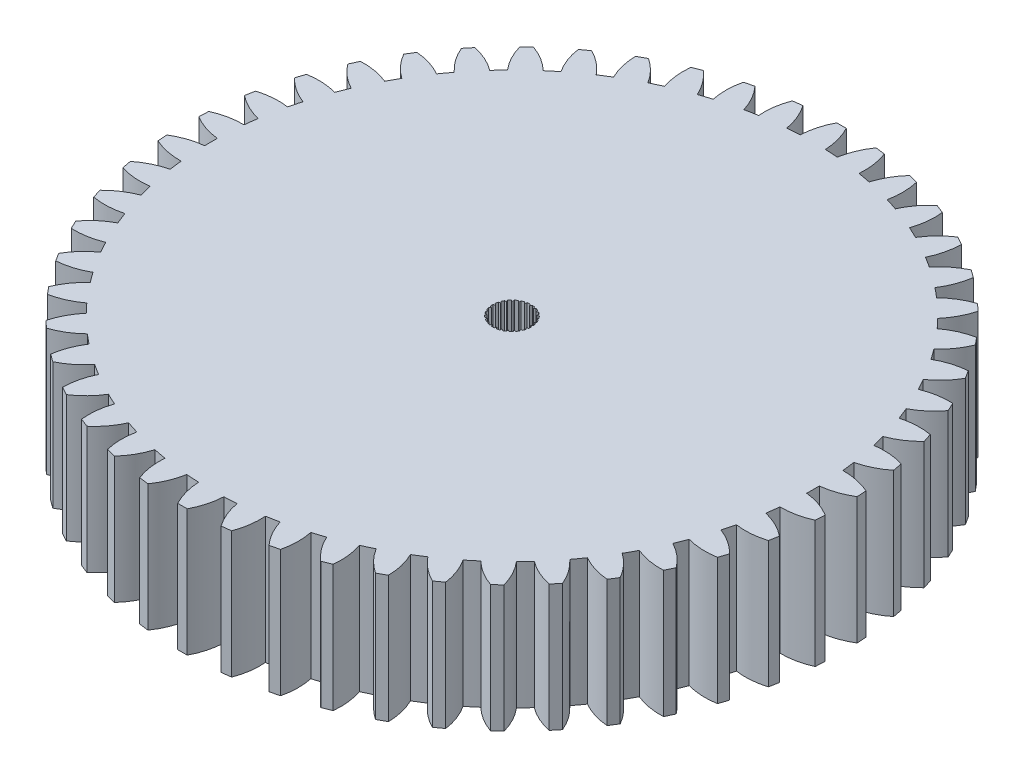
SolidWorks part; units mm, degrees
ref_plane "Front Plane" through (0, 0, 0) normal (0, 0, 1) x (1, 0, 0)
ref_plane "Top Plane" through (0, 0, 0) normal (0, 1, 0) x (1, 0, 0)
ref_plane "Right Plane" through (0, 0, 0) normal (1, 0, 0) x (0, 0, -1)
sketch "Sketch2" plane through (0, 0, 0) normal (0, 1, 0) x (1, 0, 0)
  line L0 (0, -10.2886) -> (0, 10.2886) construction
  line L1 (0, 0) -> (0.6267, 4.1579) construction
  line L2 (0, 0) -> (-0.6267, 4.1579) construction
  line L3 (0, 0) -> (0.5497, 17.4914) construction
  line L4 (0, 0) -> (-0.5497, 17.4914) construction
  line L5 (-0.1565, 3.046) -> (0, 2.775)
  line L6 (0, 2.775) -> (0.1565, 3.046)
  line L7 (-0.75, 51.9946) -> (0.75, 51.9946)
  line L8 (0.6901, 2.6878) -> (0.909, 2.9114)
  line L9 (7.8676, 46.3212) -> (7.9539, 46.8293)
  line L10 (3.8992, 46.8226) -> (3.9419, 47.3362)
  line L11 (0.606, 2.9892) -> (0.6901, 2.6878)
  line L12 (13.6112, 44.9699) -> (13.7605, 45.4632)
  line L13 (9.7368, 45.9647) -> (9.8436, 46.4688)
  line L14 (1.3369, 2.4318) -> (1.6045, 2.5938)
  line L15 (19.1401, 42.9094) -> (19.35, 43.38)
  line L16 (15.421, 44.3819) -> (15.5901, 44.8687)
  line L17 (1.3303, 2.7446) -> (1.3369, 2.4318)
  line L18 (24.3671, 40.1721) -> (24.6344, 40.6128)
  line L19 (20.8619, 42.0991) -> (21.0907, 42.5609)
  line L20 (1.8996, 2.0229) -> (2.1992, 2.1133)
  line L21 (29.2099, 36.8013) -> (29.5303, 37.205)
  line L22 (25.9738, 39.1525) -> (26.2587, 39.5819)
  line L23 (1.9711, 2.3275) -> (1.8996, 2.0229)
  line L24 (33.592, 32.8502) -> (33.9604, 33.2105)
  line L25 (30.6761, 35.5884) -> (31.0126, 35.9787)
  line L26 (2.343, 1.4869) -> (2.6556, 1.5)
  line L27 (37.4443, 28.381) -> (37.855, 28.6923)
  line L28 (34.8946, 31.463) -> (35.2774, 31.8081)
  line L29 (2.488, 1.7642) -> (2.343, 1.4869)
  line L30 (40.7061, 23.4641) -> (41.1526, 23.7215)
  line L31 (38.5628, 26.8415) -> (38.9858, 27.1359)
  line L32 (2.6392, 0.8575) -> (2.9453, 0.7925)
  line L33 (43.326, 18.1773) -> (43.8012, 18.3767)
  line L34 (41.6229, 21.7966) -> (42.0794, 22.0357)
  line L35 (2.8486, 1.0901) -> (2.6392, 0.8575)
  line L36 (45.2626, 12.6038) -> (45.7591, 12.742)
  line L37 (44.0265, 16.408) -> (44.5094, 16.588)
  line L38 (2.7695, 0.1742) -> (3.0498, 0.0351)
  line L39 (46.4853, 6.8315) -> (46.9952, 6.9064)
  line L40 (45.7358, 10.7606) -> (46.2375, 10.8787)
  line L41 (3.0302, 0.3474) -> (2.7695, 0.1742)
  line L42 (46.975, 0.9515) -> (47.4903, 0.9619)
  line L43 (46.7238, 4.9436) -> (47.2363, 4.9978)
  line L44 (2.7258, -0.52) -> (2.9627, -0.7244)
  line L45 (46.7238, -4.9436) -> (47.2363, -4.9978)
  line L46 (46.975, -0.9515) -> (47.4903, -0.9619)
  line L47 (3.0213, -0.4171) -> (2.7258, -0.52)
  line L48 (45.7358, -10.7606) -> (46.2375, -10.8787)
  line L49 (46.4853, -6.8315) -> (46.9952, -6.9064)
  line L50 (2.5109, -1.1815) -> (2.6895, -1.4385)
  line L51 (44.0265, -16.408) -> (44.5094, -16.588)
  line L52 (45.2626, -12.6038) -> (45.7591, -12.742)
  line L53 (2.8227, -1.1554) -> (2.5109, -1.1815)
  line L54 (41.6229, -21.7966) -> (42.0794, -22.0357)
  line L55 (43.326, -18.1773) -> (43.8012, -18.3767)
  line L56 (2.1382, -1.7689) -> (2.2472, -2.0621)
  line L57 (38.5628, -26.8415) -> (38.9858, -27.1359)
  line L58 (40.7061, -23.4641) -> (41.1526, -23.7215)
  line L59 (2.4467, -1.821) -> (2.1382, -1.7689)
  line L60 (34.8946, -31.463) -> (35.2774, -31.8081)
  line L61 (37.4443, -28.381) -> (37.855, -28.6923)
  line L62 (1.6311, -2.245) -> (1.6638, -2.5562)
  line L63 (30.6761, -35.5884) -> (31.0126, -35.9787)
  line L64 (33.592, -32.8502) -> (33.9604, -33.2105)
  line L65 (1.917, -2.3723) -> (1.6311, -2.245)
  line L66 (25.9738, -39.1525) -> (26.2587, -39.5819)
  line L67 (29.2099, -36.8013) -> (29.5303, -37.205)
  line L68 (1.0215, -2.5801) -> (0.9758, -2.8897)
  line L69 (20.8619, -42.0991) -> (21.0907, -42.5609)
  line L70 (24.3671, -40.1721) -> (24.6344, -40.6128)
  line L71 (1.2668, -2.7745) -> (1.0215, -2.5801)
  line L72 (15.421, -44.3819) -> (15.5901, -44.8687)
  line L73 (19.1401, -42.9094) -> (19.35, -43.38)
  line L74 (0.3478, -2.7531) -> (0.2265, -3.0416)
  line L75 (9.7368, -45.9647) -> (9.8436, -46.4688)
  line L76 (13.6112, -44.9699) -> (13.7605, -45.4632)
  line L77 (0.537, -3.0024) -> (0.3478, -2.7531)
  line L78 (3.8992, -46.8226) -> (3.9419, -47.3362)
  line L79 (7.8676, -46.3212) -> (7.9539, -46.8293)
  line L80 (-0.3478, -2.7531) -> (-0.537, -3.0024)
  line L81 (-2, -46.942) -> (-2.0219, -47.4569)
  line L82 (2, -46.942) -> (2.0219, -47.4569)
  line L83 (-0.2265, -3.0416) -> (-0.3478, -2.7531)
  line L84 (-7.8676, -46.3212) -> (-7.9539, -46.8293)
  line L85 (-3.8992, -46.8226) -> (-3.9419, -47.3362)
  line L86 (-1.0215, -2.5801) -> (-1.2668, -2.7745)
  line L87 (-13.6112, -44.9699) -> (-13.7605, -45.4632)
  line L88 (-9.7368, -45.9647) -> (-9.8436, -46.4688)
  line L89 (-0.9758, -2.8897) -> (-1.0215, -2.5801)
  line L90 (-19.1401, -42.9094) -> (-19.35, -43.38)
  line L91 (-15.421, -44.3819) -> (-15.5901, -44.8687)
  line L92 (-1.6311, -2.245) -> (-1.917, -2.3723)
  line L93 (-24.3671, -40.1721) -> (-24.6344, -40.6128)
  line L94 (-20.8619, -42.0991) -> (-21.0907, -42.5609)
  line L95 (-1.6638, -2.5562) -> (-1.6311, -2.245)
  line L96 (-29.2099, -36.8013) -> (-29.5303, -37.205)
  line L97 (-25.9738, -39.1525) -> (-26.2587, -39.5819)
  line L98 (-2.1382, -1.7689) -> (-2.4467, -1.821)
  line L99 (-33.592, -32.8502) -> (-33.9604, -33.2105)
  line L100 (-30.6761, -35.5884) -> (-31.0126, -35.9787)
  line L101 (-2.2472, -2.0621) -> (-2.1382, -1.7689)
  line L102 (-37.4443, -28.381) -> (-37.855, -28.6923)
  line L103 (-34.8946, -31.463) -> (-35.2774, -31.8081)
  line L104 (-2.5109, -1.1815) -> (-2.8227, -1.1554)
  line L105 (-40.7061, -23.4641) -> (-41.1526, -23.7215)
  line L106 (-38.5628, -26.8415) -> (-38.9858, -27.1359)
  line L107 (-2.6895, -1.4385) -> (-2.5109, -1.1815)
  line L108 (-43.326, -18.1773) -> (-43.8012, -18.3767)
  line L109 (-41.6229, -21.7966) -> (-42.0794, -22.0357)
  line L110 (-2.7258, -0.52) -> (-3.0213, -0.4171)
  line L111 (-45.2626, -12.6038) -> (-45.7591, -12.742)
  line L112 (-44.0265, -16.408) -> (-44.5094, -16.588)
  line L113 (-2.9627, -0.7244) -> (-2.7258, -0.52)
  line L114 (-46.4853, -6.8315) -> (-46.9952, -6.9064)
  line L115 (-45.7358, -10.7606) -> (-46.2375, -10.8787)
  line L116 (-2.7695, 0.1742) -> (-3.0302, 0.3474)
  line L117 (-46.975, -0.9515) -> (-47.4903, -0.9619)
  line L118 (-46.7238, -4.9436) -> (-47.2363, -4.9978)
  line L119 (-3.0498, 0.0351) -> (-2.7695, 0.1742)
  line L120 (-46.7238, 4.9436) -> (-47.2363, 4.9978)
  line L121 (-46.975, 0.9515) -> (-47.4903, 0.9619)
  line L122 (-2.6392, 0.8575) -> (-2.8486, 1.0901)
  line L123 (-45.7358, 10.7606) -> (-46.2375, 10.8787)
  line L124 (-46.4853, 6.8315) -> (-46.9952, 6.9064)
  line L125 (-2.9453, 0.7925) -> (-2.6392, 0.8575)
  line L126 (-44.0265, 16.408) -> (-44.5094, 16.588)
  line L127 (-45.2626, 12.6038) -> (-45.7591, 12.742)
  line L128 (-2.343, 1.4869) -> (-2.488, 1.7642)
  line L129 (-41.6229, 21.7966) -> (-42.0794, 22.0357)
  line L130 (-43.326, 18.1773) -> (-43.8012, 18.3767)
  line L131 (-2.6556, 1.5) -> (-2.343, 1.4869)
  line L132 (-38.5628, 26.8415) -> (-38.9858, 27.1359)
  line L133 (-40.7061, 23.4641) -> (-41.1526, 23.7215)
  line L134 (-1.8996, 2.0229) -> (-1.9711, 2.3275)
  line L135 (-34.8946, 31.463) -> (-35.2774, 31.8081)
  line L136 (-37.4443, 28.381) -> (-37.855, 28.6923)
  line L137 (-2.1992, 2.1133) -> (-1.8996, 2.0229)
  line L138 (-30.6761, 35.5884) -> (-31.0126, 35.9787)
  line L139 (-33.592, 32.8502) -> (-33.9604, 33.2105)
  line L140 (-1.3369, 2.4318) -> (-1.3303, 2.7446)
  line L141 (-25.9738, 39.1525) -> (-26.2587, 39.5819)
  line L142 (-29.2099, 36.8013) -> (-29.5303, 37.205)
  line L143 (-1.6045, 2.5938) -> (-1.3369, 2.4318)
  line L144 (-20.8619, 42.0991) -> (-21.0907, 42.5609)
  line L145 (-24.3671, 40.1721) -> (-24.6344, 40.6128)
  line L146 (-0.6901, 2.6878) -> (-0.606, 2.9892)
  line L147 (-15.421, 44.3819) -> (-15.5901, 44.8687)
  line L148 (-19.1401, 42.9094) -> (-19.35, 43.38)
  line L149 (-0.909, 2.9114) -> (-0.6901, 2.6878)
  line L150 (-9.7368, 45.9647) -> (-9.8436, 46.4688)
  line L151 (-13.6112, 44.9699) -> (-13.7605, 45.4632)
  line L153 (-3.8992, 46.8226) -> (-3.9419, 47.3362)
  line L154 (-7.8676, 46.3212) -> (-7.9539, 46.8293)
  circle A0 centre (0, 0) radius 46.9846 construction
  circle A1 centre (0, 0) radius 2.775 construction
  circle A2 centre (0, 0) radius 3.05
  circle A24 centre (0, 0) radius 47.5
  circle A25 centre (0, 0) radius 50 construction
  circle A26 centre (0, 0) radius 52 construction
  arc A27 (0.75, 51.9946) -> (2, 46.942) centre (-8.7153, 46.972) cw
  arc A28 (-0.75, 51.9946) -> (-2, 46.942) centre (8.7153, 46.972) ccw
  point P7 (0, 0)
  point P30 (1.5705, 49.9753)
  point P78 (0, 0)
  point P139 (0, 0)
  point P226 (0, 0)
  dimension "D1" = 5.55
  dimension "D3" = 6.1
  dimension "D5" = 93.9693
  dimension "D6" = 95
  dimension "D7" = 100
  dimension "D8" = 104
  dimension "D2" = 8.571
  dimension "D9" = 1.8
  dimension "D11" = 1.5
  dimension "D12" = 4
  dimension "D4" = 60
  dimension "D10" = 30
  dimension "D13" = 25
extrude "Boss-Extrude1" add sketch "Sketch2" along normal blind 20 contours A24 | A2 region at (0, 0, -46.1565)
extrude "Boss-Extrude2" add sketch "Sketch2<4>" along normal up to surface (20 mm away) contours L7 A28 A24 A27 region at (0, 0, -49.443) up to face at (0, 20, 47.5)
sketch "Sketch2<4>" plane through (0, 0, 0) normal (0, 1, 0) x (1, 0, 0) same geometry as "Sketch2"
pattern_circular "CirPattern1" count 50 over 360 about axis through (0, 20, 0) along (0, 1, 0) of "Boss-Extrude2"
extrude "Cut-Extrude2" cut sketch "Sketch2<7>" against normal blind 10 from surface contours L77 A2 L68 L71 L62 L65 L56 L59 L50 L53 L44 L47 L38 L41 L32 L35 L26 L29 L20 L23 L14 L17 L8 L11 L6 L5 L146 L149 L140 L143 L134 L137 L128 L131 L122 region at (0, 0, 0) starting at face at (0, 20, 0)
sketch "Sketch2<7>" plane through (0, 0, 0) normal (0, 1, 0) x (1, 0, 0) same geometry as "Sketch2"
sketch "Sketch3" plane through (0, 0, 0) normal (0, -1, 0) x (1, 0, 0)
  circle A0 centre (0, 0) radius 5
  dimension "D1" = 10
extrude "Cut-Extrude3" cut sketch "Sketch3" against normal up to surface (10 mm away) up to face at (0, 10, 0)
equation "\"Module\"= 2"
equation "\"Teeth\"= 50"
equation "\"Pitch Diameter\"= \"Module\" * \"Teeth\""
equation "\"Outer Diamter\"= \"Pitch Diameter\" + ( 2 * \"Module\" )"
equation "\"Root Diameter\"= \"Pitch Diameter\" - ( 2.5 * \"Module\" )"
equation "\"Base Diamter\"= \"Pitch Diameter\" * cos ( 20 )"
equation "\"D5@Sketch2\"=\"Base Diamter\""
equation "\"D6@Sketch2\"=\"Root Diameter\""
equation "\"D8@Sketch2\"=\"Outer Diamter\""
equation "\"D9@Sketch2\"=90 / \"Teeth\""
